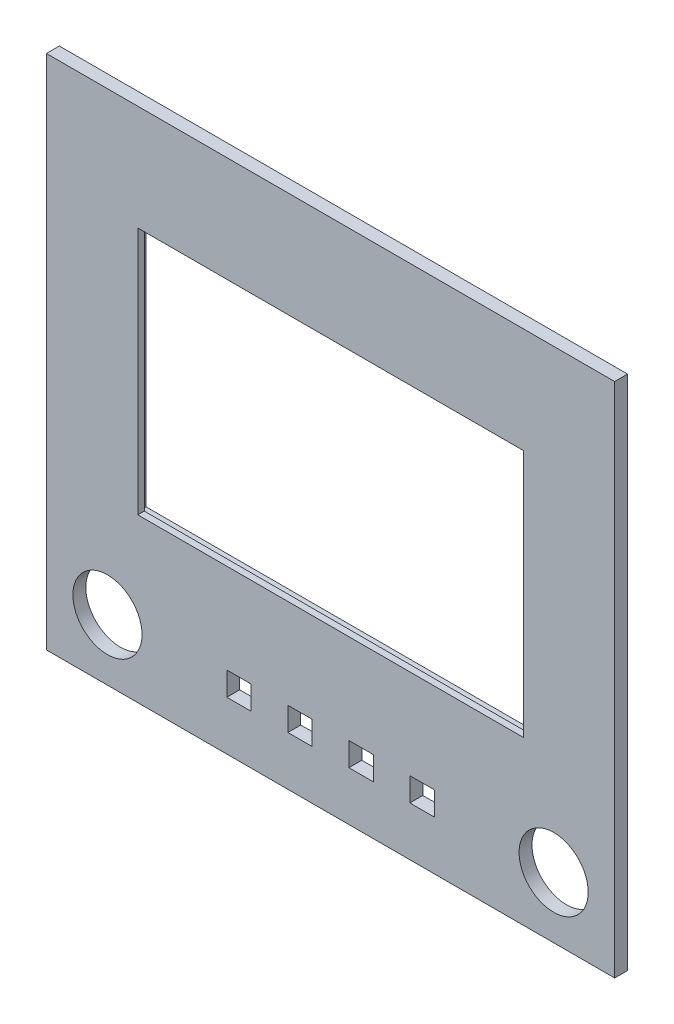
SolidWorks part; units mm, degrees
ref_plane "Front Plane" through (0, 0, 0) normal (0, 0, 1) x (1, 0, 0)
ref_plane "Top Plane" through (0, 0, 0) normal (0, 1, 0) x (1, 0, 0)
ref_plane "Right Plane" through (0, 0, 0) normal (1, 0, 0) x (0, 0, -1)
sketch "Sketch1" plane through (0, 0, 0) normal (0, 0, 1) x (1, 0, 0)
  line L0 (-10.5, -52.64) -> (-10.5, -58.44)
  line L1 (-47.385, -30.54) -> (47.385, -30.54)
  line L2 (-47.385, -30.54) -> (-47.385, 30.54)
  line L3 (-47.385, 30.54) -> (47.385, 30.54)
  line L4 (47.385, -30.54) -> (47.385, 30.54)
  line L5 (-47.385, -30.54) -> (47.385, 30.54) construction
  line L6 (-47.385, 30.54) -> (47.385, -30.54) construction
  line L7 (-69.85, 56.46) -> (69.85, 56.46)
  line L8 (-69.85, 56.46) -> (-69.85, -70.54)
  line L9 (-69.85, -70.54) -> (69.85, -70.54)
  line L10 (69.85, 56.46) -> (69.85, -70.54)
  line L11 (-25.5, -52.64) -> (-19.5, -52.64)
  line L12 (-25.5, -52.64) -> (-25.5, -58.44)
  line L13 (-25.5, -58.44) -> (-19.5, -58.44)
  line L14 (-19.5, -52.64) -> (-19.5, -58.44)
  line L15 (-54.85, -55.54) -> (54.85, -55.54) construction
  line L16 (-10.5, -52.64) -> (-4.5, -52.64)
  line L17 (-4.5, -52.64) -> (-4.5, -58.44)
  line L18 (-10.5, -58.44) -> (-4.5, -58.44)
  line L19 (4.5, -52.64) -> (4.5, -58.44)
  line L20 (4.5, -52.64) -> (10.5, -52.64)
  line L21 (10.5, -52.64) -> (10.5, -58.44)
  line L22 (4.5, -58.44) -> (10.5, -58.44)
  line L23 (19.5, -52.64) -> (19.5, -58.44)
  line L24 (19.5, -52.64) -> (25.5, -52.64)
  line L25 (25.5, -52.64) -> (25.5, -58.44)
  line L26 (19.5, -58.44) -> (25.5, -58.44)
  line L27 (-4.5, -55.54) -> (4.5, -55.54) construction
  line L28 (0, -70.54) -> (0, -53.44) construction
  line L29 (-4.5, -55.54) -> (4.5, -55.54) construction
  circle A0 centre (-54.85, -55.54) radius 8.5
  circle A1 centre (54.85, -55.54) radius 8.5
  point P0 (0, 0)
  point P16 (-25.5, -55.54)
  dimension "D12" = 17
  dimension "D13" = 17
  dimension "D1" = 61.08
  dimension "D2" = 94.77
  dimension "D3" = 139.7
  dimension "D4" = 127
  dimension "D7" = 40
  dimension "D8" = 15
  dimension "D9" = 15
  dimension "D10" = 15
  dimension "D11" = 15
  dimension "D14" = 6
  dimension "D15" = 5.8
  dimension "D16" = 4
extrude "Boss-Extrude1" add sketch "Sketch1" along normal blind 3.175
sketch "Sketch3" plane through (0, 0, 0) normal (0, 0, -1) x (-1, 0, 0)
  line L0 (47.385, 30.54) -> (47.385, -30.54) construction
  line L1 (47.385, -30.54) -> (-47.385, -30.54) construction
  line L2 (-47.385, -30.54) -> (-47.385, 30.54) construction
  line L3 (-47.385, 30.54) -> (47.385, 30.54) construction
  line L4 (47.385, 30.54) -> (47.385, -30.54)
  line L5 (47.385, -30.54) -> (-47.385, -30.54)
  line L6 (-47.385, -30.54) -> (-47.385, 30.54)
  line L7 (-47.385, 30.54) -> (47.385, 30.54)
  line L9 (-48.5, 31) -> (48.5, 31)
  line L10 (-48.5, 31) -> (-48.5, -31)
  line L11 (-48.5, -31) -> (48.5, -31)
  line L12 (48.5, 31) -> (48.5, -31)
  line L13 (-48.5, 31) -> (48.5, -31) construction
  line L14 (-48.5, -31) -> (48.5, 31) construction
  point P2 (0, 0)
  dimension "D1" = 97
  dimension "D2" = 62
extrude "Cut-Extrude1" cut sketch "Sketch3" against normal blind 1.5875
